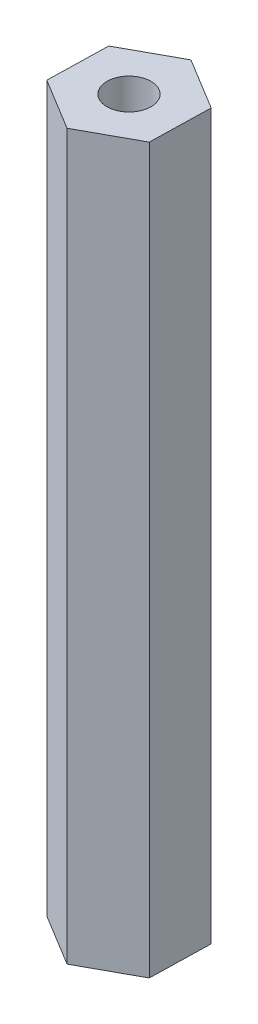
SolidWorks part; units mm, degrees
material "AISI 316 Annealed Stainless Steel Bar (SS)"
ref_plane "Front Plane" through (0, 0, 0) normal (0, 0, 1) x (1, 0, 0)
ref_plane "Top Plane" through (0, 0, 0) normal (0, 1, 0) x (1, 0, 0)
ref_plane "Right Plane" through (0, 0, 0) normal (1, 0, 0) x (0, 0, -1)
sketch "Sketch1" plane through (0, 0, 0) normal (0, 1, 0) x (1, 0, 0)
  line L1 (5.0651, 2.7709) -> (0.1329, 5.772)
  line L2 (0.1329, 5.772) -> (-4.9322, 3.0011)
  line L3 (-4.9322, 3.0011) -> (-5.0651, -2.7709)
  line L4 (-5.0651, -2.7709) -> (-0.1329, -5.772)
  line L5 (-0.1329, -5.772) -> (4.9322, -3.0011)
  line L6 (4.9322, -3.0011) -> (5.0651, 2.7709)
  circle A0 centre (0, 0) radius 5 construction
  circle A1 centre (0, 0) radius 2.1
  dimension "D2" = 4.2
  dimension "D1" = 10
extrude "Boss-Extrude1" add sketch "Sketch1" along normal mid plane 69 contours L1 L2 L3 L4 L5 L6
extrude "Cut-Extrude1" cut sketch "Sketch1<3>" against normal through all from offset 41.5 contours A1 region at (0, 0, 0)
sketch "Sketch1<3>" plane through (0, 0, 0) normal (0, 1, 0) x (1, 0, 0) same geometry as "Sketch1"
cosmetic thread "Cosmetic Thread1" parameters "D1"=15, "D2"=5
cosmetic thread "Cosmetic Thread2" parameters "D1"=15, "D2"=5
